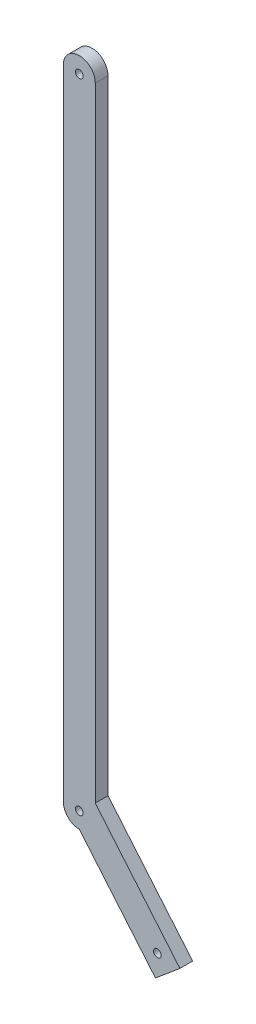
SolidWorks part; units mm, degrees
ref_plane "Front Plane" through (0, 0, 0) normal (0, 0, 1) x (1, 0, 0)
ref_plane "Top Plane" through (0, 0, 0) normal (0, 1, 0) x (1, 0, 0)
ref_plane "Right Plane" through (0, 0, 0) normal (1, 0, 0) x (0, 0, -1)
sketch "Sketch1" plane through (0, 0, 0) normal (0, 0, 1) x (1, 0, 0)
  line L0 (-12.5, 0) -> (-12.5, -500)
  line L1 (12.5, 0) -> (12.5, -500)
  line L2 (-12.5, -250) -> (12.5, -250) construction
  circle A0 centre (0, 0) radius 3
  arc A1 (12.5, 0) -> (-12.5, 0) centre (0, 0) ccw
  arc A2 (12.5, -500) -> (-12.5, -500) centre (0, -500) cw
  circle A3 centre (0, -500) radius 3
  dimension "D1" = 6
  dimension "D2" = 25
  dimension "D3" = 500
extrude "Boss-Extrude1" add sketch "Sketch1" along normal blind 10
sketch "Sketch2" plane through (0, 0, 10) normal (0, 0, 1) x (1, 0, 0)
  line L1 (12.5, -500) -> (-12.5, -500) construction
  line L4 (61.2002, -565.989) -> (69.235, -575.5645) construction
  line L6 (12.5, -488.5038) -> (78.8106, -567.5297)
  line L7 (12.5, -500) -> (12.5, 0) construction
  line L8 (78.8106, -567.5297) -> (59.6594, -583.5994)
  line L9 (59.6594, -583.5994) -> (0, -512.5)
  line L11 (12.5, -488.5038) -> (0, -512.5)
  line L12 (12.5, -500) -> (12.5, 0) construction
  arc A0 (-12.5, -500) -> (12.5, -500) centre (0, -500) ccw construction
  circle A2 centre (61.2002, -565.989) radius 3
  dimension "D2" = 6
  dimension "D1" = 12.5
  dimension "D3" = 90
  dimension "D4" = 140
extrude "Boss-Extrude3" add sketch "Sketch2" against normal up to surface (10 mm away) up to face at (0, -250, 0)
